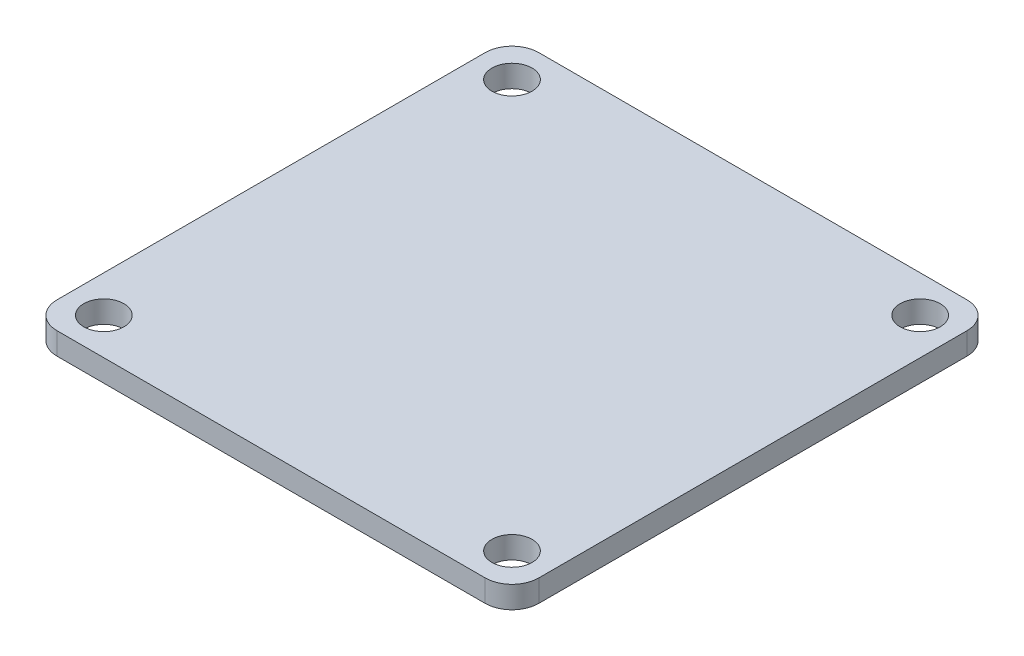
SolidWorks part; units mm, degrees
ref_plane "Front Plane" through (0, 0, 0) normal (0, 0, 1) x (1, 0, 0)
ref_plane "Top Plane" through (0, 0, 0) normal (0, 1, 0) x (1, 0, 0)
ref_plane "Right Plane" through (0, 0, 0) normal (1, 0, 0) x (0, 0, -1)
sketch "Sketch1" plane through (0, 0, 0) normal (0, 1, 0) x (1, 0, 0)
  line L0 (0, 18) -> (0, -18) construction
  line L1 (-18, 18) -> (18, 18)
  line L2 (-18, 18) -> (-18, -18)
  line L3 (-18, -18) -> (18, -18)
  line L4 (18, 18) -> (18, -18)
  line L5 (-18, 18) -> (18, -18) construction
  line L6 (-18, -18) -> (18, 18) construction
  line L7 (-18, 0) -> (18, 0) construction
  circle A0 centre (-15.25, 15.25) radius 1.5
  circle A1 centre (15.25, 15.25) radius 1.5
  circle A2 centre (15.25, -15.25) radius 1.5
  circle A3 centre (-15.25, -15.25) radius 1.5
  point P0 (0, 0)
  dimension "D2" = 3
  dimension "D1" = 36
  dimension "D3" = 30.5
extrude "Base shape" add sketch "Sketch1" along normal blind 1.65
fillet "Rounded corners" radius 2 4 edges at (-18, 0.825, -18) (18, 0.825, -18) (18, 0.825, 18) (-18, 0.825, 18)
